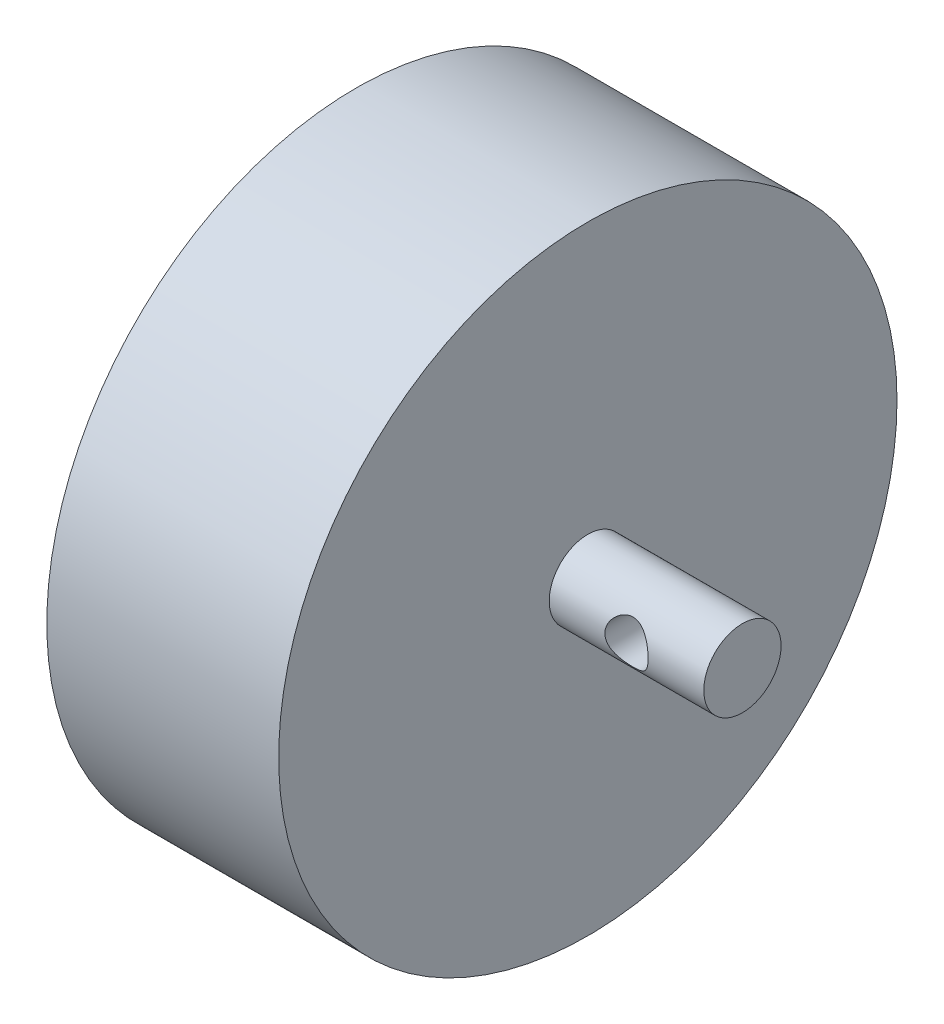
SolidWorks part; units mm, degrees
ref_plane "前视基准面" through (0, 0, 0) normal (0, 0, 1) x (1, 0, 0)
ref_plane "上视基准面" through (0, 0, 0) normal (0, 1, 0) x (1, 0, 0)
ref_plane "右视基准面" through (0, 0, 0) normal (1, 0, 0) x (0, 0, -1)
sketch "草图1" plane through (0, 0, 0) normal (1, 0, 0) x (0, 0, -1)
  circle A0 centre (0, 0) radius 3.5
extrude "凸台-拉伸1" add sketch "草图1" along normal blind 3
sketch "草图2" plane through (3, 0, 0) normal (1, 0, 0) x (0, 0, -1)
  circle A0 centre (0, 0) radius 20
extrude "凸台-拉伸2" add sketch "草图2" along normal blind 15
sketch "草图3" plane through (18, 0, 0) normal (1, 0, 0) x (0, 0, -1)
  circle A0 centre (0, 0) radius 2.5
extrude "凸台-拉伸3" add sketch "草图3" along normal blind 10
sketch "草图4" plane through (0, 0, 0) normal (0, 0, 1) x (1, 0, 0)
  line L0 (18, -20) -> (18, 20) construction
  circle A0 centre (23, 0) radius 1.4
  dimension "D1" = 5
  dimension "D2" = 2.8
extrude "切除-拉伸1" cut sketch "草图4" against normal blind 10 and the other way blind 10
sketch "草图5" plane through (3, 0, 0) normal (-1, 0, 0) x (0, 0, 1)
  circle A0 centre (0, 0) radius 6.5 construction
  point P3 (-6.5, 0)
  point P4 (0, -6.5)
  point P5 (6.5, 0)
  point P6 (0, 6.5)
hole_wizard "M3 螺纹孔1" positions "3D草图1" profile "草图6" tap size "M3" standard "GB"
sketch3d "3D草图1"
  point P0 (3, 0, 6.5)
  point P3 (3, -6.5, 0)
  point P6 (3, 0, -6.5)
  point P9 (3, 6.5, 0)
sketch "草图6" plane through (3, 0, 6.5) normal (0, 1, 0) x (0, 0, 1)
  line L0 (0, 0) -> (0, 7.5)
  line L1 (0, 7.5) -> (1.25, 6.7489)
  line L2 (1.25, 6.7489) -> (1.25, 0)
  line L5 (1.25, 0) -> (0, 0)
  line L10 (0, 7.5) -> (-1.25, 6.7489) construction
  line L11 (0, -6.35) -> (0, 107.95) construction
  dimension "螺纹孔钻头直径" = 2.5
  dimension "螺纹孔钻头深度" = 7.5
  dimension "导头角度" = 118
cosmetic thread "孔螺蚊线1" parameters "D1"=6, "D2"=3
cosmetic thread "孔螺蚊线2" parameters "D1"=6, "D2"=3
cosmetic thread "孔螺蚊线3" parameters "D1"=6, "D2"=3
cosmetic thread "孔螺蚊线4" parameters "D1"=6, "D2"=3
